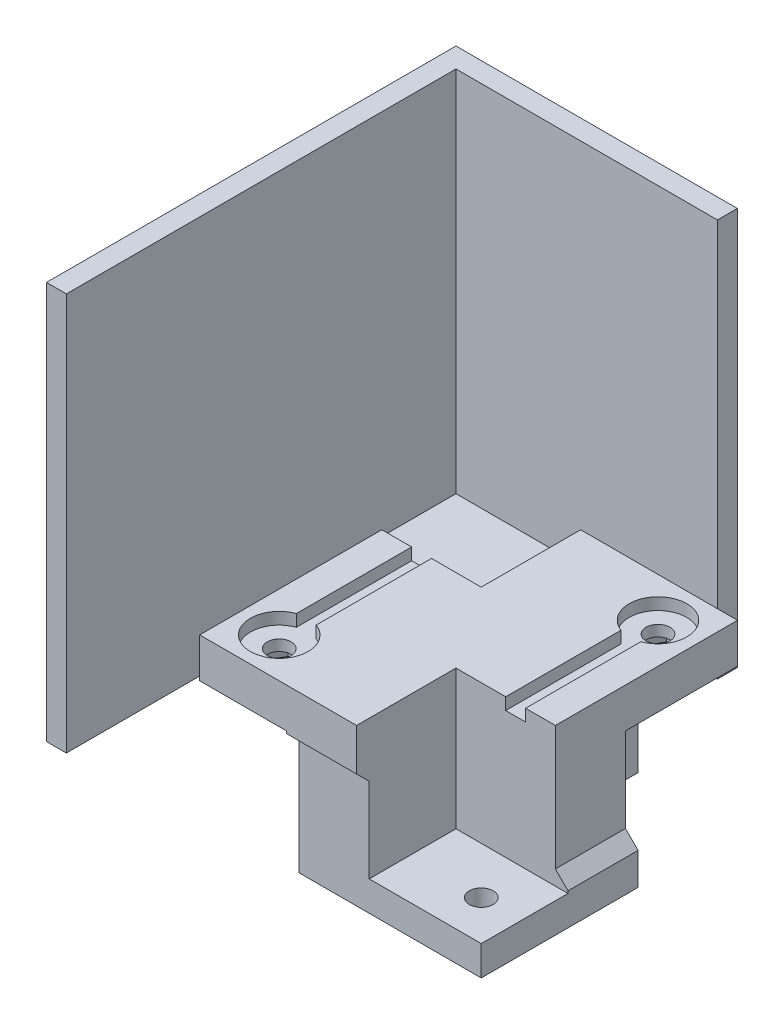
SolidWorks part; units mm, degrees
ref_plane "Front Plane" through (0, 0, 0) normal (0, 0, 1) x (1, 0, 0)
ref_plane "Top Plane" through (0, 0, 0) normal (0, 1, 0) x (1, 0, 0)
ref_plane "Right Plane" through (0, 0, 0) normal (1, 0, 0) x (0, 0, -1)
sketch "Sketch1" plane through (0, 0, 0) normal (0, 1, 0) x (1, 0, 0)
  line L0 (-14.16, -12.89) -> (-14.16, 12.89)
  line L1 (-10.16, -8.89) -> (10.16, -8.89) construction
  line L2 (-10.16, -8.89) -> (-10.16, 8.89) construction
  line L3 (-10.16, 8.89) -> (10.16, 8.89) construction
  line L4 (10.16, -8.89) -> (10.16, 8.89) construction
  line L5 (-10.16, -8.89) -> (10.16, 8.89) construction
  line L6 (-10.16, 8.89) -> (10.16, -8.89) construction
  line L7 (-14.16, 12.89) -> (14.16, 12.89)
  line L8 (14.16, -12.89) -> (14.16, 12.89)
  line L9 (-14.16, -12.89) -> (14.16, -12.89)
  circle A0 centre (-10.16, 8.89) radius 1.2
  circle A1 centre (10.16, 8.89) radius 1.2
  circle A2 centre (10.16, -8.89) radius 1.2
  circle A3 centre (-10.16, -8.89) radius 1.2
  point P0 (0, 0)
  dimension "D4" = 2.4
  dimension "D1" = 17.78
  dimension "D2" = 20.32
  dimension "D3" = 4
extrude "Boss-Extrude1" add sketch "Sketch1" along normal blind 3
ref_plane "Plane1" through (0, 13, 0) normal (0, 1, 0) x (1, 0, 0)
sketch "Sketch4" plane through (0, 13, 0) normal (0, 1, 0) x (1, 0, 0)
  line L0 (-12.89, -14.16) -> (12.89, -14.16)
  line L1 (-8.89, -10.16) -> (8.89, -10.16) construction
  line L2 (-8.89, -10.16) -> (-8.89, 10.16) construction
  line L3 (-8.89, 10.16) -> (8.89, 10.16) construction
  line L4 (8.89, -10.16) -> (8.89, 10.16) construction
  line L5 (-8.89, -10.16) -> (8.89, 10.16) construction
  line L6 (-8.89, 10.16) -> (8.89, -10.16) construction
  line L7 (12.89, -14.16) -> (12.89, 14.16)
  line L8 (-12.89, 14.16) -> (12.89, 14.16)
  line L9 (-12.89, -14.16) -> (-12.89, 14.16)
  circle A0 centre (-8.89, 10.16) radius 1.2
  circle A1 centre (8.89, 10.16) radius 1.2
  circle A2 centre (-8.89, -10.16) radius 1.2
  circle A3 centre (8.89, -10.16) radius 1.2
  point P0 (0, 0)
  dimension "D4" = 2.4
  dimension "D1" = 20.32
  dimension "D2" = 17.78
  dimension "D3" = 4
extrude "Boss-Extrude2" add sketch "Sketch4" along normal blind 4 separate body
sketch "Sketch5" plane through (0, 17, 0) normal (0, 1, 0) x (1, 0, 0)
  line L1 (-12.89, 14.16) -> (-2.89, 14.16)
  line L2 (-12.89, 14.16) -> (-12.89, 4.16)
  line L3 (-12.89, 4.16) -> (-2.89, 4.16)
  line L4 (-2.89, 14.16) -> (-2.89, 4.16)
  line L5 (12.89, -14.16) -> (2.89, -14.16)
  line L6 (12.89, -14.16) -> (12.89, -4.16)
  line L7 (12.89, -4.16) -> (2.89, -4.16)
  line L8 (2.89, -14.16) -> (2.89, -4.16)
  dimension "D1" = 10
extrude "Cut-Extrude2" cut sketch "Sketch5" against normal up to next (4 mm away)
sketch "Sketch8" plane through (0, 0, 0) normal (0, -1, 0) x (1, 0, 0)
  line L1 (-14.16, 12.89) -> (-4.16, 12.89)
  line L2 (-14.16, 12.89) -> (-14.16, 2.89)
  line L3 (-14.16, 2.89) -> (-4.16, 2.89)
  line L4 (-4.16, 12.89) -> (-4.16, 2.89)
  line L5 (14.16, -12.89) -> (4.16, -12.89)
  line L6 (14.16, -12.89) -> (14.16, -2.89)
  line L7 (14.16, -2.89) -> (4.16, -2.89)
  line L8 (4.16, -12.89) -> (4.16, -2.89)
  dimension "D1" = 10
extrude "Cut-Extrude3" cut sketch "Sketch8" against normal up to next (3 mm away)
sketch "Sketch9" plane through (0, 13, 0) normal (0, -1, 0) x (1, 0, 0)
  line L8 (14.16, 12.89) -> (-4.16, 12.89)
  line L9 (-4.16, 12.89) -> (-4.16, 2.89)
  line L10 (-4.16, 2.89) -> (-14.16, 2.89)
  line L11 (-14.16, 2.89) -> (-14.16, -12.89)
  line L12 (-14.16, -12.89) -> (4.16, -12.89)
  line L13 (4.16, -12.89) -> (4.16, -2.89)
  line L14 (4.16, -2.89) -> (14.16, -2.89)
  line L15 (14.16, -2.89) -> (14.16, 12.89)
  line L16 (14.16, 12.89) -> (-4.16, 12.89)
  line L17 (-4.16, 12.89) -> (-4.16, 2.89)
  line L18 (-4.16, 2.89) -> (-14.16, 2.89)
  line L19 (-14.16, 2.89) -> (-14.16, -12.89)
  line L20 (-14.16, -12.89) -> (4.16, -12.89)
  line L21 (4.16, -12.89) -> (4.16, -2.89)
  line L22 (4.16, -2.89) -> (14.16, -2.89)
  line L23 (14.16, -2.89) -> (14.16, 12.89)
  line L24 (-2.89, -4.16) -> (-2.89, -14.16)
  line L25 (-2.89, -14.16) -> (12.89, -14.16)
  line L26 (12.89, -14.16) -> (12.89, 4.16)
  line L27 (12.89, 4.16) -> (2.89, 4.16)
  line L28 (2.89, 4.16) -> (2.89, 14.16)
  line L29 (2.89, 14.16) -> (-12.89, 14.16)
  line L30 (-12.89, 14.16) -> (-12.89, -4.16)
  line L31 (-12.89, -4.16) -> (-2.89, -4.16)
  line L32 (-2.89, -4.16) -> (-2.89, -14.16)
  line L33 (-2.89, -14.16) -> (12.89, -14.16)
  line L34 (12.89, -14.16) -> (12.89, 4.16)
  line L35 (12.89, 4.16) -> (2.89, 4.16)
  line L36 (2.89, 4.16) -> (2.89, 14.16)
  line L37 (2.89, 14.16) -> (-12.89, 14.16)
  line L38 (-12.89, 14.16) -> (-12.89, -4.16)
  line L39 (-12.89, -4.16) -> (-2.89, -4.16)
  line M33 (-2.89, -4.16) -> (-2.89, -14.16)
  line M35 (12.89, -14.16) -> (12.89, 4.16)
  line M36 (12.89, 4.16) -> (2.89, 4.16)
  line M37 (2.89, 4.16) -> (2.89, 14.16)
  line M39 (-12.89, 14.16) -> (-12.89, -4.16)
  line M40 (-12.89, -4.16) -> (-2.89, -4.16)
  dimension "D1" = 0
  dimension "D2" = 0
extrude "Boss-Extrude3" add sketch "Sketch9" along normal up to surface (10 mm away) contours L21 L22 L16 L17 L18 L20 M35 M36 M37 M39 M40 M33 region at (0, 13, 0) up to face at (0, 3, 0)
sketch "Sketch3" plane through (0, 17, 0) normal (0, 1, 0) x (1, 0, 0)
  circle A0 centre (8.89, 10.16) radius 2.9
  circle A4 centre (-8.89, -10.16) radius 2.9
  dimension "D1" = 5.8
extrude "Cut-Extrude4" cut sketch "Sketch3" against normal blind 1.2
chamfer "Chamfer1" distance 1.5 angle 45 4 edges at (0.635, 13, -12.89) (-0.635, 13, 12.89) (12.89, 3, 0.635) (-12.89, 3, -0.635)
sketch "Sketch10" plane through (0, 3, 0) normal (0, 1, 0) x (1, 0, 0)
  line L0 (-28.3021, 12.89) -> (-14.16, -2.89)
  line L3 (-14.16, 27.0321) -> (-28.3021, 27.0321)
  line L4 (-28.3021, 12.89) -> (-28.3021, 27.0321)
  line L5 (-14.16, 27.0321) -> (4.16, 12.89)
  line L6 (-28.3021, 12.89) -> (-14.16, 12.89) construction
  line L7 (-14.16, 27.0321) -> (-14.16, 12.89) construction
  line L8 (-14.16, 12.89) -> (-28.3021, 27.0321) construction
  line L12 (-4.16, -12.89) -> (14.16, -12.89)
  line L13 (-4.16, -2.89) -> (-4.16, -12.89)
  line L14 (-14.16, -2.89) -> (-4.16, -2.89)
  line L15 (-14.16, 12.89) -> (-14.16, -2.89)
  line L16 (4.16, 12.89) -> (-14.16, 12.89)
  line L17 (4.16, 2.89) -> (4.16, 12.89)
  line L18 (14.16, 2.89) -> (4.16, 2.89)
  line L19 (14.16, -12.89) -> (14.16, 2.89)
  line L23 (-14.16, 12.89) -> (-14.16, -2.89)
  line L24 (4.16, 12.89) -> (-14.16, 12.89)
  dimension "D2" = 20
  dimension "D1" = 0
extrude "Boss-Extrude4" add sketch "Sketch10" against normal up to surface (3 mm away) up to face at (0, 0, 0)
sketch "Sketch11" plane through (0, 3, 0) normal (0, 1, 0) x (1, 0, 0)
  line L0 (-28.3021, -14.16) -> (-28.3021, 27.0321)
  line L1 (-28.3021, 27.0321) -> (0, 27.0321)
extrude "Extrude-Thin1" add sketch "Sketch11" along normal offset from surface 40 and the other way up to surface (3 mm away) thin up to face at (-5.6604, 0, -5.4064) other way up to face at (-5.6604, 0, -5.4064) thin type one direction wall 2
sketch "Sketch12" plane through (0, 13, 0) normal (0, -1, 0) x (1, 0, 0)
  line L1 (-10.0765, 12.215) -> (-11.2629, 10.16)
  line L2 (-11.2629, 10.16) -> (-10.0765, 8.105)
  line L3 (-10.0765, 8.105) -> (-7.7035, 8.105)
  line L4 (-7.7035, 8.105) -> (-6.5171, 10.16)
  line L5 (-6.5171, 10.16) -> (-7.7035, 12.215)
  line L6 (-7.7035, 12.215) -> (-10.0765, 12.215)
  line L7 (10.0765, -12.215) -> (11.2629, -10.16)
  line L8 (11.2629, -10.16) -> (10.0765, -8.105)
  line L9 (10.0765, -8.105) -> (7.7035, -8.105)
  line L10 (7.7035, -8.105) -> (6.5171, -10.16)
  line L11 (6.5171, -10.16) -> (7.7035, -12.215)
  line L12 (7.7035, -12.215) -> (10.0765, -12.215)
  circle A0 centre (-8.89, 10.16) radius 2.055 construction
  circle A1 centre (8.89, -10.16) radius 2.055 construction
  dimension "D1" = 4.11
extrude "Cut-Extrude5" cut sketch "Sketch12" against normal blind 1.7
chamfer "Chamfer2" distance 0.5 angle 45 12 edges at (8.89, 13, -8.105) (10.6697, 13, -9.1325) (10.6697, 13, -11.1875) (8.89, 13, -12.215) (7.1103, 13, -11.1875) (7.1103, 13, -9.1325) (-8.89, 13, 8.105) (-7.1103, 13, 9.1325) (-7.1103, 13, 11.1875) (-8.89, 13, 12.215) (-10.6697, 13, 11.1875) (-10.6697, 13, 9.1325)
sketch "Sketch13" plane through (0, 17, 0) normal (0, 1, 0) x (1, 0, 0)
  line L1 (-9.89, -7.4379) -> (-7.89, -7.4379)
  line L2 (-9.89, -7.4379) -> (-9.89, 4.16)
  line L3 (-9.89, 4.16) -> (-7.89, 4.16)
  line L4 (-7.89, -7.4379) -> (-7.89, 4.16)
  line L5 (-2.89, 4.16) -> (-14.16, 4.16) construction
  line L6 (12.89, -4.16) -> (2.89, -4.16) construction
  line L7 (7.89, 7.4379) -> (9.89, 7.4379)
  line L8 (7.89, 7.4379) -> (7.89, -4.16)
  line L9 (7.89, -4.16) -> (9.89, -4.16)
  line L10 (9.89, 7.4379) -> (9.89, -4.16)
  circle A0 centre (-8.89, -10.16) radius 2.9 construction
  circle A1 centre (8.89, 10.16) radius 2.9 construction
  circle A2 centre (8.89, 10.16) radius 2.9
  circle A3 centre (-8.89, -10.16) radius 2.9 construction
  circle A4 centre (-8.89, -10.16) radius 2.9
  point P7 (-8.89, -10.16)
  point P8 (-8.89, -7.4379)
  point P19 (8.89, 10.16)
  point P20 (8.89, 7.4379)
  circle M9 centre (8.89, 10.16) radius 2.9
  circle M10 centre (-8.89, -10.16) radius 2.9
  line M13 (-2.89, 4.16) -> (-12.89, 4.16)
  line M17 (2.89, -4.16) -> (12.89, -4.16)
  dimension "D1" = 2
extrude "Cut-Extrude6" cut sketch "Sketch13" against normal up to surface (1.2 mm away) contours L4 L2 M10 M13 | L10 L8 M9 M17 region at (-8.89, 17, 1.5794) region at (8.89, 17, -1.5794) up to face at (-8.89, 15.8, 11.36)
equation "\"D1@Sketch1\"=0.7in"
equation "\"D2@Sketch1\"=0.8in"
equation "\"D1@Sketch12\"=3.91+0.2"
